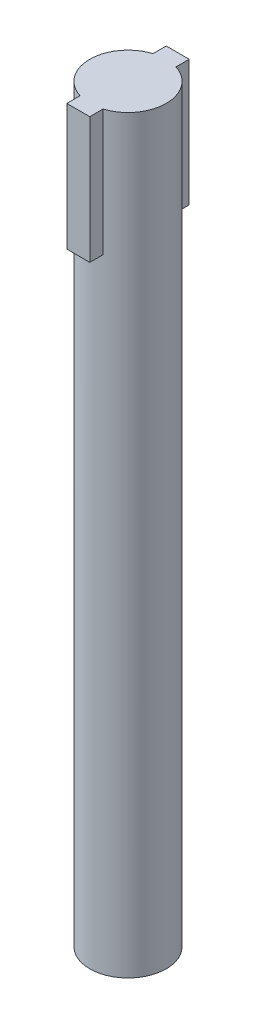
SolidWorks part; units mm, degrees
material "PLA personnalisé"
ref_plane "Plan de face" through (0, 0, 0) normal (0, 0, 1) x (1, 0, 0)
ref_plane "Plan de dessus" through (0, 0, 0) normal (0, 1, 0) x (1, 0, 0)
ref_plane "Plan de droite" through (0, 0, 0) normal (1, 0, 0) x (0, 0, -1)
sketch "Esquisse1" plane through (0, 0, 0) normal (0, 1, 0) x (1, 0, 0)
  circle A0 centre (0, 0) radius 5
  dimension "D1" = 10
extrude "Boss.-Extru.1" add sketch "Esquisse1" along normal blind 8 and the other way blind 90
sketch "Esquisse2" plane through (0, 8, 0) normal (0, 1, 0) x (1, 0, 0)
  line L0 (-1.5, 0) -> (1.5, 0)
  line L1 (1.5, 6.5) -> (1.5, -6.5)
  line L2 (1.5, -6.5) -> (-1.5, -6.5)
  line L3 (-1.5, -6.5) -> (-1.5, 6.5)
  line L4 (1.5, 6.5) -> (-1.5, 6.5)
  circle M5 centre (0, 0) radius 5
  dimension "D1" = 1.5
  dimension "D2" = 3
  dimension "D3" = 6.5
extrude "Boss.-Extru.2" add sketch "Esquisse2" against normal blind 16.5 contours L1 L4 L3 M5 | L3 L2 L1 M5 | L3 L1 L0 M5 | L3 L0 L1 M5 region at (0, 8, -2.4625) region at (0, 8, 2.4625) region at (0, 8, 5.7105) region at (0, 8, -5.7105)
